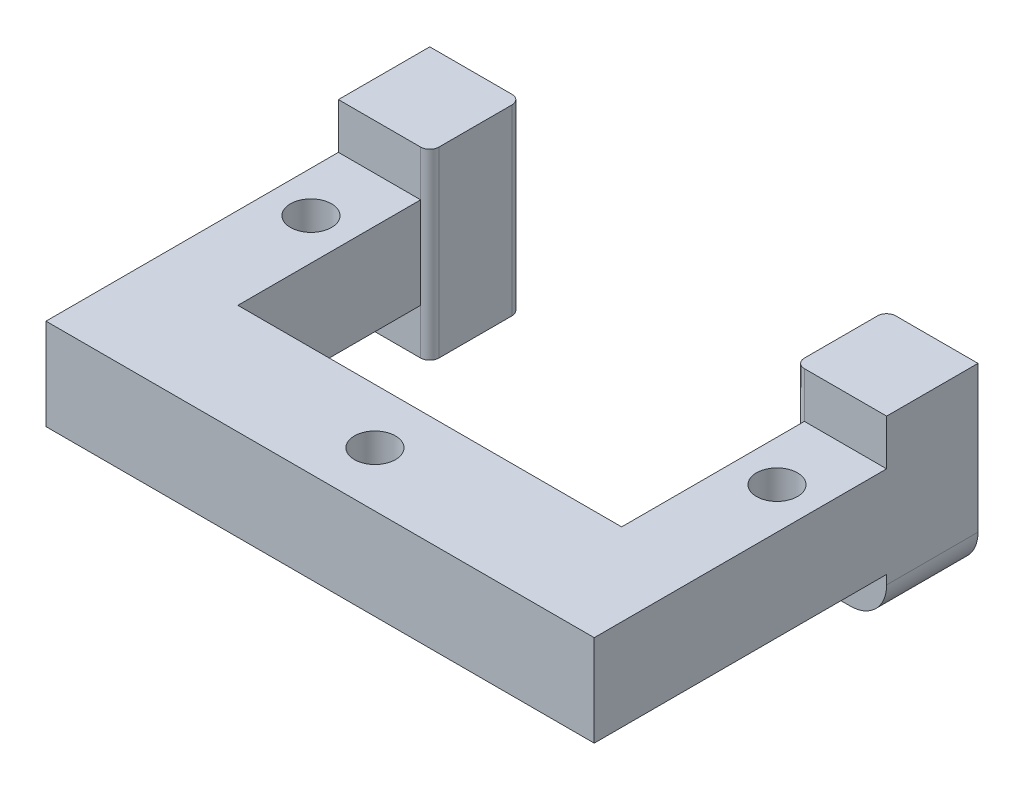
SolidWorks part; units mm, degrees
material "ABS"
ref_plane "Front Plane" through (0, 0, 0) normal (0, 0, 1) x (1, 0, 0)
ref_plane "Top Plane" through (0, 0, 0) normal (0, 1, 0) x (1, 0, 0)
ref_plane "Right Plane" through (0, 0, 0) normal (1, 0, 0) x (0, 0, -1)
sketch "Sketch1" plane through (0, 0, 0) normal (0, 1, 0) x (1, 0, 0)
  line L0 (0, 30.876) -> (0, -57.2152) construction
  line L1 (-20, 0) -> (-30, 0)
  line L2 (-30, 0) -> (-30, -42)
  line L3 (-30, -42) -> (30, -42)
  line L4 (30, -42) -> (30, 0)
  line L5 (30, 0) -> (20, 0)
  line L6 (20, 0) -> (20, -10)
  line L7 (20, -30) -> (-20, -30)
  line L8 (-20, -10) -> (-20, 0)
  line L9 (-20, -10) -> (-21, -10)
  line L10 (-21, -10) -> (-21, -30)
  line L11 (-21, -30) -> (-20, -30)
  line L12 (21, -30) -> (20, -30)
  line L13 (20, -10) -> (21, -10)
  line L14 (21, -10) -> (21, -30)
  point P5 (-25, 0)
  dimension "D1" = 40
  dimension "D2" = 10
  dimension "D3" = 30
  dimension "D4" = 12
  dimension "D5" = 10
  dimension "D6" = 1
extrude "Boss-Extrude1" add sketch "Sketch1" along normal blind 20
sketch "Sketch2" plane through (0, 0, 0) normal (0, 0, -1) x (-1, 0, 0)
  line L0 (-25, 20) -> (-25, 0) construction
  line L1 (-30, 20) -> (-20, 20) construction
  line L2 (-30, 0) -> (-20, 0) construction
  line L4 (0, 0) -> (0, 42.0055) construction
  circle A2 centre (-24.25, 14.79) radius 2.75
  circle A3 centre (-24.25, 4.79) radius 2.75
  point P6 (-24.25, 14.79)
  point P11 (-24.25, 4.79)
  dimension "D4" = 5.5
  dimension "D1" = 5.21
  dimension "D2" = 24.25
  dimension "D3" = 15.21
extrude "Cut-Extrude1" cut sketch "Sketch2" against normal blind 8
mirror "Mirror1" about plane through (0, 0, 0) normal (1, 0, 0) of "Cut-Extrude1"
fillet "Fillet1" radius 1 4 edges at (-20, 10, 0) (20, 10, 0) (20, 10, 10) (-20, 10, 10)
sketch "Sketch7" plane through (0, 0, 0) normal (0, -1, 0) x (1, 0, 0)
  line L0 (-21, 10) -> (-30, 10)
  line L1 (21, 10) -> (30, 10)
  line L10 (21, 30) -> (21, 10)
  line L11 (20, 9) -> (20, 1)
  line L12 (21, 0) -> (30, 0)
  line L13 (30, 0) -> (30, 42)
  line L14 (30, 42) -> (-30, 42)
  line L15 (-30, 42) -> (-30, 0)
  line L16 (-30, 0) -> (-21, 0)
  line L17 (-20, 1) -> (-20, 9)
  line L18 (-21, 10) -> (-21, 30)
  line L19 (-21, 30) -> (21, 30)
  line L20 (21, 30) -> (21, 10)
  line L21 (20, 9) -> (20, 1)
  line L22 (21, 0) -> (30, 0)
  line L23 (30, 0) -> (30, 42)
  line L24 (30, 42) -> (-30, 42)
  line L25 (-30, 42) -> (-30, 0)
  line L26 (-30, 0) -> (-21, 0)
  line L27 (-20, 1) -> (-20, 9)
  line L28 (-21, 10) -> (-21, 30)
  line L29 (-21, 30) -> (21, 30)
  arc A4 (21, 10) -> (20, 9) centre (21, 9) ccw
  arc A5 (20, 1) -> (21, 0) centre (21, 1) ccw
  arc A6 (-21, 0) -> (-20, 1) centre (-21, 1) ccw
  arc A7 (-20, 9) -> (-21, 10) centre (-21, 9) ccw
  arc A8 (21, 10) -> (20, 9) centre (21, 9) ccw
  arc A9 (20, 1) -> (21, 0) centre (21, 1) ccw
  arc A10 (-21, 0) -> (-20, 1) centre (-21, 1) ccw
  arc A11 (-20, 9) -> (-21, 10) centre (-21, 9) ccw
  line M15 (21, 30) -> (21, 10)
  line M20 (30, 0) -> (30, 42)
  line M21 (30, 42) -> (-30, 42)
  line M22 (-30, 42) -> (-30, 0)
  line M27 (-21, 10) -> (-21, 30)
  line M28 (-21, 30) -> (21, 30)
  dimension "D1" = 0
extrude "Cut-Extrude3" cut sketch "Sketch7" against normal blind 5 contours L1 L0 M15 M20 M21 M22 M27 M28 region at (0, 0, 30.6667)
ref_plane "Plane2" through (0, 10, 0) normal (0, 1, 0) x (1, 0, 0)
mirror "Mirror2" about plane through (0, 10, 0) normal (0, 1, 0) of "Cut-Extrude3"
sketch "Sketch8" plane through (0, 15, 0) normal (0, 1, 0) x (1, 0, 0)
  line L8 (21, -10) -> (21, -30)
  line L9 (21, -30) -> (-21, -30)
  line L10 (-21, -30) -> (-21, -10)
  line L11 (-21, -10) -> (-30, -10)
  line L12 (-30, -10) -> (-30, -42)
  line L13 (-30, -42) -> (30, -42)
  line L14 (30, -42) -> (30, -10)
  line L15 (30, -10) -> (21, -10)
  line L16 (21, -10) -> (21, -30)
  line L17 (21, -30) -> (-21, -30)
  line L18 (-21, -30) -> (-21, -10)
  line L19 (-21, -10) -> (-30, -10)
  line L20 (-30, -10) -> (-30, -42)
  line L21 (-30, -42) -> (30, -42)
  line L22 (30, -42) -> (30, -10)
  line L23 (30, -10) -> (21, -10)
  dimension "D1" = 0
sketch "Sketch9" plane through (0, 5, 0) normal (0, -1, 0) x (1, 0, 0)
  line L0 (-30, 36) -> (30, 36) construction
  line L1 (-25.5, 10) -> (-25.5, 42) construction
  line L2 (0, 51.8317) -> (0, -8.1141) construction
  line L8 (21, 30) -> (21, 10)
  line L9 (21, 10) -> (30, 10)
  line L10 (30, 10) -> (30, 42)
  line L11 (30, 42) -> (-30, 42)
  line L12 (-30, 42) -> (-30, 10)
  line L13 (-30, 10) -> (-21, 10)
  line L14 (-21, 10) -> (-21, 30)
  line L15 (-21, 30) -> (21, 30)
  line L16 (21, 30) -> (21, 10)
  line L17 (21, 10) -> (30, 10)
  line L18 (30, 10) -> (30, 42)
  line L19 (30, 42) -> (-30, 42)
  line L21 (-30, 10) -> (-21, 10)
  line L23 (-21, 30) -> (21, 30)
  circle A0 centre (0, 36) radius 2.25
  circle A1 centre (-25.5, 17.5) radius 2.25
  circle A2 centre (25.5, 17.5) radius 2.25
  dimension "D2" = 4.5
  dimension "D3" = 7.5
  dimension "D1" = 0
extrude "Cut-Extrude5" cut sketch "Sketch9" against normal through all contours A1 | A2 | A0 region at (-25.5, 5, 17.5) region at (25.5, 5, 17.5)
fillet "Fillet2" radius 4 2 edges at (30, 0, 5) (-30, 0, 5)
